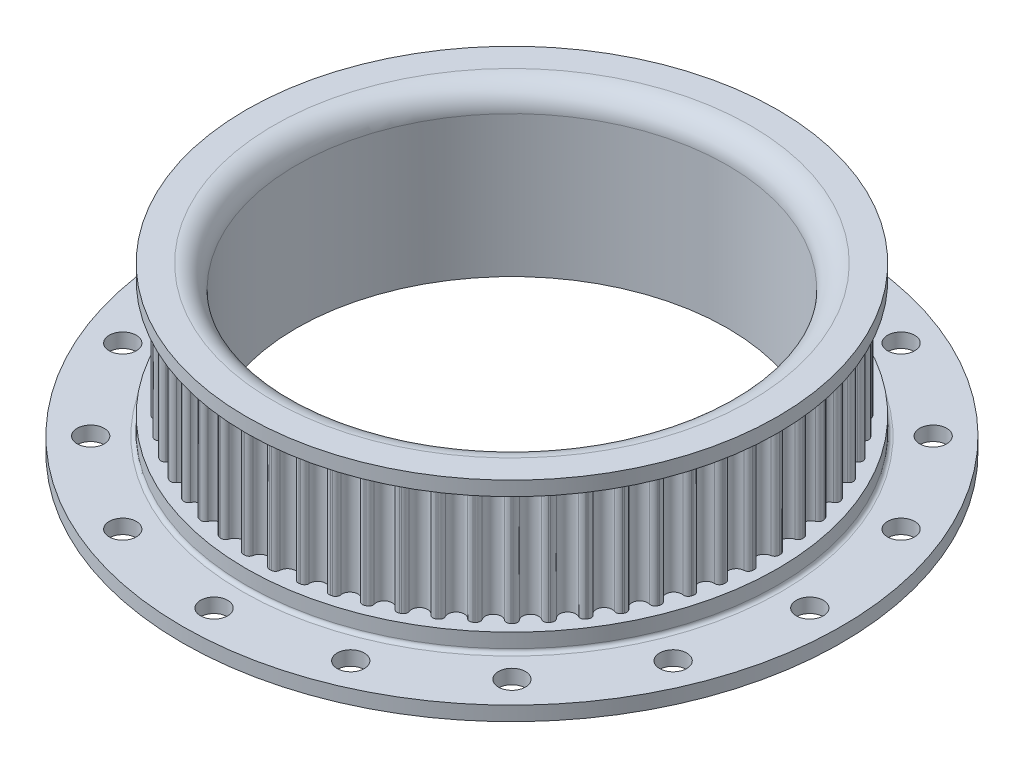
SolidWorks part; units mm, degrees
ref_plane "Front Plane" through (0, 0, 0) normal (0, 0, 1) x (1, 0, 0)
ref_plane "Top Plane" through (0, 0, 0) normal (0, 1, 0) x (1, 0, 0)
ref_plane "Right Plane" through (0, 0, 0) normal (1, 0, 0) x (0, 0, -1)
sketch "Sketch1" plane through (0, 0, 0) normal (0, 1, 0) x (1, 0, 0)
  line L0 (0, 0) -> (0, 28.2667) construction
  line L1 (0, 0) -> (2.9202, 27.7837) construction
  circle A0 centre (0, 0) radius 28.2667 construction
  circle A1 centre (0, 0) radius 27.0467 construction
  circle A2 centre (0, 27.9367) radius 0.89 construction
  circle A5 centre (2.9202, 27.7837) radius 0.89 construction
  arc A6 (0, 27.0467) -> (0.8804, 27.8061) centre (0, 27.9367) ccw
  arc A7 (0.8804, 27.8061) -> (1.3997, 28.2321) centre (1.3749, 27.7327) cw
  arc A8 (1.559, 28.2237) -> (2.031, 27.7458) centre (1.5314, 27.7245) cw
  arc A9 (2.8272, 26.8986) -> (2.031, 27.7458) centre (2.9202, 27.7837) cw
  arc A10 (1.3997, 28.2321) -> (1.559, 28.2237) centre (0, 0) cw
  arc A11 (0, 27.0467) -> (2.8272, 26.8986) centre (0, 0) ccw
  dimension "D1" = 56.5335
  dimension "D3" = 1.78
  dimension "D4" = 0.5
  dimension "D2" = 1.22
  dimension "D5" = 6
extrude "Boss-Extrude1" add sketch "Sketch1" along normal mid plane 13 contours A6 A11 A9 A8 A7 region at (0.001, 0, -0.0192)
ref_axis "Axis1" through (0, 3.3, 0) along (0, -1, 0)
pattern_circular "CirPattern1" count 60 over 360 about axis through (0, 3.3, 0) along (0, -1, 0) of "Boss-Extrude1"
sketch "Sketch2" plane through (0, 0, 0) normal (1, 0, 0) x (0, 0, -1)
  line L10 (0, 6.5) -> (29.4415, 6.5) construction
  line L11 (0, 6.5) -> (0, 8.0875) construction
  line L12 (0, 8.0875) -> (29.4415, 8.0875) construction
  line L15 (29.4415, 6.5) -> (29.4415, 8.0875) construction
  line L20 (0, 3.3) -> (0, -3.3) construction
  line L22 (29.4415, 8.0875) -> (0, 8.0875)
  line L23 (29.4415, 8.0875) -> (29.4415, 6.5)
  line L24 (29.4415, 6.5) -> (0, 6.5)
  line L25 (0, 8.0875) -> (0, 6.5)
  dimension "D1" = 1.5875
  dimension "D2" = 29.4415
  dimension "D3" = 6.5
revolve "Revolve3" add sketch "Sketch2" angle 360 about axis through (0, 3.3, 0) along (0, -1, 0) region at (0, 7.2937, -14.7207)
mirror "Mirror1" about plane through (0, 0, 0) normal (0, 1, 0) of "Revolve3"
sketch "Sketch3" plane through (0, 0, 0) normal (0, -1, 0) x (-1, 0, 0)
  circle A0 centre (0, 0) radius 23.8852
  dimension "D1" = 47.7705
extrude "Cut-Extrude1" cut sketch "Sketch3" against normal through all both and the other way through all
sketch "Sketch5" plane through (0, 0, 0) normal (0, 0, 1) x (1, 0, 0)
  line L0 (29.4415, -6.5) -> (-29.4415, -6.5) construction
  line L1 (-29.854, -8.5) -> (-36.5125, -8.5)
  line L2 (-36.5125, -8.5) -> (-36.5125, -10.0875)
  line L3 (-36.5125, -10.0875) -> (-23.8852, -10.0875)
  line L4 (-23.8852, -10.0875) -> (-23.8852, -8.0875)
  line L5 (-29.4415, -8.0875) -> (29.4415, -8.0875) construction
  line L6 (-23.8852, -8.0875) -> (-29.4415, -8.0875)
  arc A0 (-29.4415, -8.0875) -> (-29.854, -8.5) centre (-29.854, -8.0875) cw
  dimension "D1" = 2
  dimension "D2" = 36.5125
  dimension "D3" = 1.5875
revolve "Revolve4" add sketch "Sketch5" angle 360 about axis through (0, 3.3, 0) along (0, -1, 0)
sketch "Sketch6" plane through (0, -8.5, 0) normal (0, 1, 0) x (1, 0, 0)
  line L0 (-30.488, 12.6286) -> (0, 0) construction
  line L1 (0, 0) -> (-36.5125, 0) construction
  circle A0 centre (-30.488, 12.6286) radius 1.5
  circle A1 centre (0, 0) radius 36.5125 construction
  dimension "D2" = 3
  dimension "D1" = 33
  dimension "D3" = 22.5
extrude "Cut-Extrude2" cut sketch "Sketch6" against normal through all
pattern_circular "CirPattern2" count 16 over 360 about axis through (0, 3.3, 0) along (0, -1, 0) of "Cut-Extrude2"
fillet "Fillet1" radius 2.54 1 edges at (0, 8.0875, -23.8852)
equation "\"TEETH_NUM\"= 60"
equation "\"TOOTH_PITCH\"= 3mm"
equation "\"PITCH_LINE_OFFSET\"= .015in"
equation "\"DIAMETER_PER_GROOVE\"= \"OUTSIDE_DIAMETER\" / \"TEETH_NUM\" * 1in"
equation "\"PITCH_DIAMETER\"= ( ( \"TEETH_NUM\" * 3 - 1.31 ) / 3.1415 + .415 ) * 1mm"
equation "\"OUTSIDE_DIAMETER\"= \"PITCH_DIAMETER\" - \"PITCH_LINE_OFFSET\" * 2"
equation "\"D1@Sketch1\"=\"OUTSIDE_DIAMETER\""
equation "\"TOOTH_HEIGHT\"= 1.22mm"
equation "\"D2@Sketch1\"=\"TOOTH_HEIGHT\""
equation "\"TOOTH_DIAMETER\"= 1.78mm"
equation "\"INTERNAL_RADIUS\"= .5mm"
equation "\"D3@Sketch1\"=\"TOOTH_DIAMETER\""
equation "\"D5@Sketch1\"=360 / \"TEETH_NUM\""
equation "\"D4@Sketch1\"=\"INTERNAL_RADIUS\""
equation "\"D1@CirPattern1\"=\"TEETH_NUM\""
equation "\"BELT_GAP\"= 13mm"
equation "\"D2@Sketch2\"=\"PITCH_DIAMETER\"/2+1/32"
equation "\"D3@Sketch2\"=\"BELT_GAP\"/2"
equation "\"D1@Sketch3\"=\"PITCH_DIAMETER\"-.375"
equation "\"D1@Boss-Extrude1\"=\"BELT_GAP\""
equation "\"center_offset\"=0.75"
equation "\"Bearing_Diameter\"= 58mm"
equation "\"bolt_on_feature\"=16"
equation "\"D1@CirPattern2\"=\"bolt_on_feature\""
